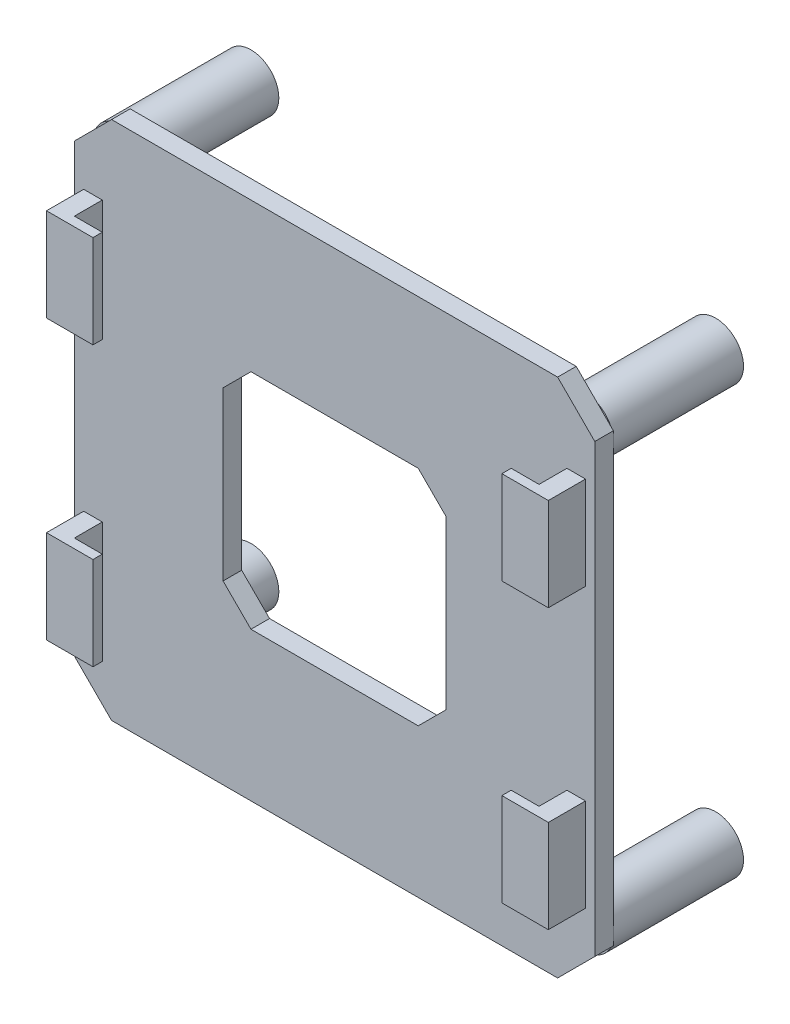
SolidWorks part; units mm, degrees
ref_plane "前视基准面" through (0, 0, 0) normal (0, 0, 1) x (1, 0, 0)
ref_plane "上视基准面" through (0, 0, 0) normal (0, 1, 0) x (1, 0, 0)
ref_plane "右视基准面" through (0, 0, 0) normal (1, 0, 0) x (0, 0, -1)
other "Configuration Table"
sketch "草图1" plane through (0, 0, 0) normal (0, 0, 1) x (1, 0, 0)
  line L0 (-24, -28) -> (24, -28)
  line L1 (24, -28) -> (28, -24)
  line L2 (28, -24) -> (28, 24)
  line L3 (28, 24) -> (24, 28)
  line L4 (24, 28) -> (-24, 28)
  line L5 (-24, 28) -> (-28, 24)
  line L6 (-28, 24) -> (-28, -24)
  line L7 (-28, -24) -> (-24, -28)
  line L8 (-9, -12) -> (9, -12)
  line L9 (9, -12) -> (12, -9)
  line L10 (12, -9) -> (12, 9)
  line L11 (12, 9) -> (9, 12)
  line L12 (9, 12) -> (-9, 12)
  line L13 (-9, 12) -> (-12, 9)
  line L14 (-12, 9) -> (-12, -9)
  line L15 (-12, -9) -> (-9, -12)
extrude "电调承托环_与飞控叠放" add sketch "草图1" along normal blind 2 from offset 6
sketch "草图2" plane through (0, 0, 0) normal (0, 0, 1) x (1, 0, 0)
  circle A0 centre (-25, -23) radius 3
extrude "托框立脚_-1_-1" add sketch "草图2" along normal blind 14 from offset 20
sketch "草图3" plane through (0, 0, 0) normal (0, 0, 1) x (1, 0, 0)
  circle A1 centre (-25, -23) radius 1.65
extrude "立脚M3导孔_-1_-1" cut sketch "草图3" along normal blind 14 from offset 20
sketch "草图4" plane through (0, 0, 0) normal (0, 0, 1) x (1, 0, 0)
  line L0 (-27, -20) -> (-25, -20)
  line L1 (-25, -20) -> (-25, -10)
  line L2 (-25, -10) -> (-27, -10)
  line L3 (-27, -10) -> (-27, -20)
extrude "电调侧卡壁_-1_-1" add sketch "草图4" along normal blind 3 from offset 4
sketch "草图5" plane through (0, 0, 0) normal (0, 0, 1) x (1, 0, 0)
  line L0 (-27, -20) -> (-22, -20)
  line L1 (-22, -20) -> (-22, -10)
  line L2 (-22, -10) -> (-27, -10)
  line L3 (-27, -10) -> (-27, -20)
extrude "电调上卡唇_-1_-1" add sketch "草图5" along normal blind 1 from offset 1
sketch "草图6" plane through (0, 0, 0) normal (0, 0, 1) x (1, 0, 0)
  circle A0 centre (-25, 23) radius 3
extrude "托框立脚_-1_1" add sketch "草图6" along normal blind 14 from offset 20
sketch "草图7" plane through (0, 0, 0) normal (0, 0, 1) x (1, 0, 0)
  circle A1 centre (-25, 23) radius 1.65
extrude "立脚M3导孔_-1_1" cut sketch "草图7" along normal blind 14 from offset 20
sketch "草图8" plane through (0, 0, 0) normal (0, 0, 1) x (1, 0, 0)
  line L0 (-27, 10) -> (-25, 10)
  line L1 (-25, 10) -> (-25, 20)
  line L2 (-25, 20) -> (-27, 20)
  line L3 (-27, 20) -> (-27, 10)
extrude "电调侧卡壁_-1_1" add sketch "草图8" along normal blind 3 from offset 4
sketch "草图9" plane through (0, 0, 0) normal (0, 0, 1) x (1, 0, 0)
  line L0 (-27, 10) -> (-22, 10)
  line L1 (-22, 10) -> (-22, 20)
  line L2 (-22, 20) -> (-27, 20)
  line L3 (-27, 20) -> (-27, 10)
extrude "电调上卡唇_-1_1" add sketch "草图9" along normal blind 1 from offset 1
sketch "草图10" plane through (0, 0, 0) normal (0, 0, 1) x (1, 0, 0)
  circle A0 centre (25, -23) radius 3
extrude "托框立脚_1_-1" add sketch "草图10" along normal blind 14 from offset 20
sketch "草图11" plane through (0, 0, 0) normal (0, 0, 1) x (1, 0, 0)
  circle A1 centre (25, -23) radius 1.65
extrude "立脚M3导孔_1_-1" cut sketch "草图11" along normal blind 14 from offset 20
sketch "草图12" plane through (0, 0, 0) normal (0, 0, 1) x (1, 0, 0)
  line L0 (25, -20) -> (27, -20)
  line L1 (27, -20) -> (27, -10)
  line L2 (27, -10) -> (25, -10)
  line L3 (25, -10) -> (25, -20)
extrude "电调侧卡壁_1_-1" add sketch "草图12" along normal blind 3 from offset 4
sketch "草图13" plane through (0, 0, 0) normal (0, 0, 1) x (1, 0, 0)
  line L0 (22, -20) -> (27, -20)
  line L1 (27, -20) -> (27, -10)
  line L2 (27, -10) -> (22, -10)
  line L3 (22, -10) -> (22, -20)
extrude "电调上卡唇_1_-1" add sketch "草图13" along normal blind 1 from offset 1
sketch "草图14" plane through (0, 0, 0) normal (0, 0, 1) x (1, 0, 0)
  circle A0 centre (25, 23) radius 3
extrude "托框立脚_1_1" add sketch "草图14" along normal blind 14 from offset 20
sketch "草图15" plane through (0, 0, 0) normal (0, 0, 1) x (1, 0, 0)
  circle A1 centre (25, 23) radius 1.65
extrude "立脚M3导孔_1_1" cut sketch "草图15" along normal blind 14 from offset 20
sketch "草图16" plane through (0, 0, 0) normal (0, 0, 1) x (1, 0, 0)
  line L0 (25, 10) -> (27, 10)
  line L1 (27, 10) -> (27, 20)
  line L2 (27, 20) -> (25, 20)
  line L3 (25, 20) -> (25, 10)
extrude "电调侧卡壁_1_1" add sketch "草图16" along normal blind 3 from offset 4
sketch "草图17" plane through (0, 0, 0) normal (0, 0, 1) x (1, 0, 0)
  line L0 (22, 10) -> (27, 10)
  line L1 (27, 10) -> (27, 20)
  line L2 (27, 20) -> (22, 20)
  line L3 (22, 20) -> (22, 10)
extrude "电调上卡唇_1_1" add sketch "草图17" along normal blind 1 from offset 1
